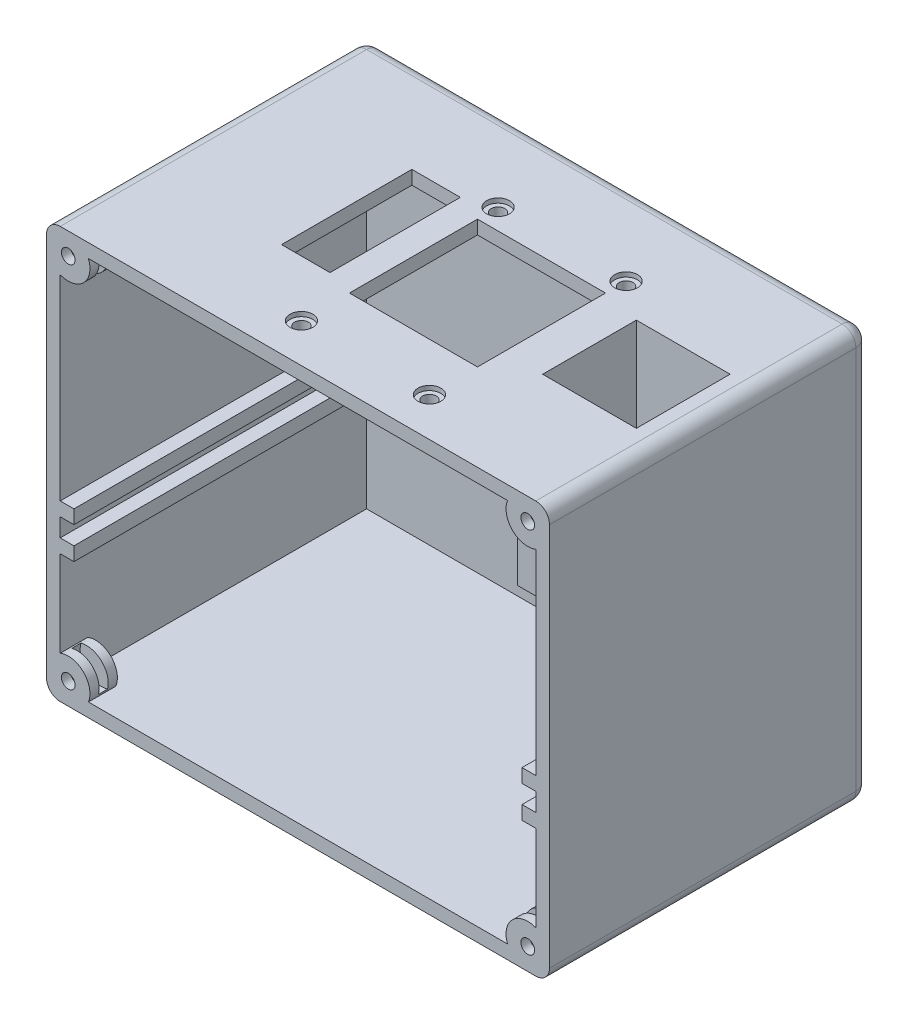
SolidWorks part; units mm, degrees
ref_plane "Płaszczyzna przednia" through (0, 0, 0) normal (0, 0, 1) x (1, 0, 0)
ref_plane "Płaszczyzna górna" through (0, 0, 0) normal (0, 1, 0) x (1, 0, 0)
ref_plane "Płaszczyzna prawa" through (0, 0, 0) normal (1, 0, 0) x (0, 0, -1)
sketch "Sketch2" plane through (0, 0, 0) normal (0, 0, 1) x (1, 0, 0)
  line L1 (55, -45) -> (-55, -45)
  line L2 (55, -45) -> (55, 45)
  line L3 (55, 45) -> (-55, 45)
  line L4 (-55, -45) -> (-55, 45)
  line L5 (55, -45) -> (-55, 45) construction
  line L6 (55, 45) -> (-55, -45) construction
  point P0 (0, 0)
  dimension "D1" = 110
  dimension "D2" = 90
extrude "Boss-Extrude1" add sketch "Sketch2" along normal blind 70
sketch "Sketch4" plane through (0, 0, 70) normal (0, 0, 1) x (1, 0, 0)
  line L0 (55, 45) -> (-55, 45) construction
  line L1 (52, -42) -> (-52, -42)
  line L2 (52, -42) -> (52, 42)
  line L3 (52, 42) -> (-52, 42)
  line L4 (-52, -42) -> (-52, 42)
  line L5 (52, -42) -> (-52, 42) construction
  line L6 (52, 42) -> (-52, -42) construction
  line L7 (-55, 45) -> (-55, -45) construction
  point P0 (0, 0)
  dimension "D1" = 3
  dimension "D2" = 3
extrude "Cut-Extrude1" cut sketch "Sketch4" against normal blind 67
fillet "Fillet6" radius 3 4 edges at (0, -45, 0) (55, 0, 0) (0, 45, 0) (-55, 0, 0)
fillet "Fillet7" radius 3 2 edges at (54.1213, 44.1213, 0.8787) (55, 45, 36.5)
fillet "Fillet8" radius 3 2 edges at (54.1213, -44.1213, 0.8787) (55, -45, 36.5)
fillet "Fillet9" radius 3 2 edges at (-54.1213, -44.1213, 0.8787) (-55, -45, 36.5)
fillet "Fillet10" radius 3 2 edges at (-54.1213, 44.1213, 0.8787) (-55, 45, 36.5)
sketch "Sketch5" plane through (0, 45, 0) normal (0, 1, 0) x (1, 0, 0)
  line L0 (52, -70) -> (52, -3) construction
  line L1 (26, -22) -> (52, -22)
  line L2 (26, -22) -> (26, -48)
  line L3 (26, -48) -> (52, -48)
  line L4 (52, -22) -> (52, -48)
  line L5 (26, -22) -> (52, -48) construction
  line L6 (26, -48) -> (52, -22) construction
  line L7 (-52, 0) -> (52, 0) construction
  point P0 (39, -35)
  dimension "D1" = 26
  dimension "D2" = 22
extrude "Boss-Extrude2" add sketch "Sketch5" against normal blind 40
sketch "Sketch7" plane through (0, 5, 0) normal (0, -1, 0) x (1, 0, 0)
  line L0 (52, 22) -> (26, 22) construction
  line L1 (28.75, 45.25) -> (49.25, 45.25)
  line L2 (28.75, 45.25) -> (28.75, 24.75)
  line L3 (28.75, 24.75) -> (49.25, 24.75)
  line L4 (49.25, 45.25) -> (49.25, 24.75)
  line L5 (28.75, 45.25) -> (49.25, 24.75) construction
  line L6 (28.75, 24.75) -> (49.25, 45.25) construction
  line L7 (52, 48) -> (52, 22) construction
  point P0 (39, 35)
  dimension "D1" = 20.5
  dimension "D2" = 2.75
  dimension "D3" = 2.75
extrude "Cut-Extrude2" cut sketch "Sketch7" against normal blind 40
sketch "Sketch9" plane through (-55, 0, 0) normal (-1, 0, 0) x (0, 0, 1)
  line L0 (3, -42) -> (70, -42) construction
  line L1 (3, -14) -> (70, -14)
  line L2 (3, -14) -> (3, -17)
  line L3 (3, -17) -> (70, -17)
  line L4 (70, -14) -> (70, -17)
  line L5 (70, 42) -> (70, -42) construction
  line L7 (3, -7) -> (70, -7)
  line L8 (3, -7) -> (3, -10)
  line L9 (3, -10) -> (70, -10)
  line L10 (70, -7) -> (70, -10)
  dimension "D1" = 3
  dimension "D2" = 25
  dimension "D3" = 4
extrude "Boss-Extrude3" add sketch "Sketch9" against normal blind 6
sketch "Sketch10" plane through (55, 0, 0) normal (1, 0, 0) x (0, 0, -1)
  line L0 (-70, -42) -> (-3, -42) construction
  line L1 (-70, -14) -> (-3, -14)
  line L2 (-70, -14) -> (-70, -17)
  line L3 (-70, -17) -> (-3, -17)
  line L4 (-3, -14) -> (-3, -17)
  line L5 (-70, -42) -> (-70, 42) construction
  line L7 (-70, -7) -> (-3, -7)
  line L8 (-70, -7) -> (-70, -10)
  line L9 (-70, -10) -> (-3, -10)
  line L10 (-3, -7) -> (-3, -10)
  dimension "D1" = 3
  dimension "D2" = 25
  dimension "D3" = 4
extrude "Boss-Extrude4" add sketch "Sketch10" against normal blind 6
sketch "Sketch12" plane through (0, 45, 0) normal (0, 1, 0) x (1, 0, 0)
  line L0 (28.75, -45.25) -> (28.75, -24.75) construction
  line L1 (-10.25, -16) -> (22.75, -16) construction
  line L2 (-10.25, -16) -> (-10.25, -64) construction
  line L3 (-10.25, -64) -> (22.75, -64) construction
  line L4 (22.75, -16) -> (22.75, -64) construction
  line L5 (-52, 0) -> (52, 0) construction
  line L7 (-7.75, -23) -> (20.25, -23)
  line L8 (-7.75, -23) -> (-7.75, -51)
  line L9 (-7.75, -51) -> (20.25, -51)
  line L10 (20.25, -23) -> (20.25, -51)
  circle A0 centre (-7.75, -18.5) radius 1.5
  circle A1 centre (20.25, -18.5) radius 1.5
  circle A2 centre (-7.75, -61.5) radius 1.5
  circle A3 centre (20.25, -61.5) radius 1.5
  dimension "D5" = 3
  dimension "D8" = 3
  dimension "D11" = 3
  dimension "D14" = 3
  dimension "D1" = 48
  dimension "D2" = 33
  dimension "D3" = 6
  dimension "D4" = 16
  dimension "D6" = 2.5
  dimension "D7" = 2.5
  dimension "D9" = 2.5
  dimension "D10" = 2.5
  dimension "D12" = 2.5
  dimension "D13" = 2.5
  dimension "D15" = 2.5
  dimension "D16" = 2.5
  dimension "D17" = 28
  dimension "D18" = 2.5
  dimension "D19" = 7
extrude "Cut-Extrude4" cut sketch "Sketch12" against normal blind 6
sketch "Sketch13" plane through (0, 45, 0) normal (0, 1, 0) x (1, 0, 0)
  line L0 (-7.75, -23) -> (-7.75, -51) construction
  line L1 (-24.35, -20.75) -> (-13.75, -20.75)
  line L2 (-24.35, -20.75) -> (-24.35, -49.25)
  line L3 (-24.35, -49.25) -> (-13.75, -49.25)
  line L4 (-13.75, -20.75) -> (-13.75, -49.25)
  line L5 (-52, 0) -> (52, 0) construction
  dimension "D1" = 10.6
  dimension "D2" = 28.5
  dimension "D3" = 6
  dimension "D4" = 20.75
extrude "Cut-Extrude5" cut sketch "Sketch13" against normal blind 6
sketch "Sketch14" plane through (0, 0, 70) normal (0, 0, 1) x (1, 0, 0)
  line L0 (52, 45) -> (-52, 45) construction
  line L1 (-55, 42) -> (-55, -42) construction
  line L2 (55, -42) -> (55, 42) construction
  line L3 (-52, -45) -> (52, -45) construction
  circle A0 centre (-50.25, 40.25) radius 4.75
  circle A1 centre (-50.25, 40.25) radius 1.5
  circle A3 centre (50.25, 40.25) radius 4.75
  circle A5 centre (50.25, 40.25) radius 1.5
  circle A6 centre (-50.25, -40.25) radius 4.75
  circle A8 centre (-50.25, -40.25) radius 1.5
  circle A9 centre (50.25, -40.25) radius 4.75
  circle A11 centre (50.25, -40.25) radius 1.5
  dimension "D1" = 9.5
  dimension "D3" = 3
  dimension "D4" = 9.5
  dimension "D6" = 3
  dimension "D7" = 9.5
  dimension "D9" = 3
  dimension "D10" = 9.5
  dimension "D12" = 3
extrude "Boss-Extrude7" add sketch "Sketch14" against normal blind 6
sketch "Sketch16" plane through (0, 0, 70) normal (0, 0, 1) x (1, 0, 0)
  circle A0 centre (-50.25, 40.25) radius 2.75
  circle A1 centre (-46.8912, 36.8912) radius 4.75
  circle A2 centre (50.25, 40.25) radius 2.75
  circle A3 centre (50.25, 40.25) radius 1.5 construction
  circle A4 centre (-50.25, 40.25) radius 1.5 construction
  circle A5 centre (-50.25, -40.25) radius 2.75
  circle A6 centre (-50.25, -40.25) radius 1.5 construction
  circle A7 centre (50.25, -40.25) radius 2.75
  circle A8 centre (50.25, -40.25) radius 1.5 construction
  circle A10 centre (46.8912, -36.8912) radius 4.75
  arc A12 (52, -35.8341) -> (45.8341, -42) centre (50.25, -40.25) ccw construction
  arc A15 (-52, 35.8341) -> (-45.8341, 42) centre (-50.25, 40.25) ccw construction
  circle A16 centre (46.8912, 36.8912) radius 4.75
  arc A17 (45.8341, 42) -> (52, 35.8341) centre (50.25, 40.25) ccw construction
  circle A18 centre (-46.8912, -36.8912) radius 4.75
  arc A19 (-45.8341, -42) -> (-52, -35.8341) centre (-50.25, -40.25) ccw construction
  arc M6 (52, -35.8341) -> (45.8341, -42) centre (50.25, -40.25) ccw
  arc M8 (-45.8341, -42) -> (-52, -35.8341) centre (-50.25, -40.25) ccw
  arc M18 (-52, 35.8341) -> (-45.8341, 42) centre (-50.25, 40.25) ccw
  arc M20 (45.8341, 42) -> (52, 35.8341) centre (50.25, 40.25) ccw
  circle M37 centre (50.25, -40.25) radius 1.5
  circle M38 centre (-50.25, 40.25) radius 1.5
  circle M39 centre (50.25, 40.25) radius 1.5
  circle M40 centre (-50.25, -40.25) radius 1.5
  dimension "D1" = 5.5
  dimension "D2" = 5.5
  dimension "D3" = 5.5
  dimension "D4" = 5.5
extrude "Cut-Extrude6" cut sketch "Sketch16" against normal blind 2 from offset 2 contours A18 A5 M40 | A18 M8 | A18 A5 M8 | A5 A18 M40 | A10 A7 M37 | A7 A10 M37 | A10 A7 M6 | A10 M6 | A16 A2 M39 | A2 A16 M39 | A2 A16 M20 | A16 M20 | A1 M18 | A1 A0 M18 | A0 A1 M38 | A1 A0 M38 region at (-49.1285, 39.1285, 70) region at (-48.1128, 38.1128, 70) region at (-48.4686, 41.4492, 70) region at (-45.813, 35.813, 70) region at (52.5466, 38.8748, 70) region at (49.1285, 39.1285, 70) region at (48.1128, 38.1128, 70) region at (45.813, 35.813, 70) region at (-49.1285, -39.1285, 70) region at (-48.1128, -38.1128, 70) region at (-51.4492, -38.4686, 70) region at (-45.813, -35.813, 70) region at (50.9015, -42.8463, 70) region at (49.1285, -39.1285, 70) region at (48.1128, -38.1128, 70) region at (45.813, -35.813, 70) offset against normal yes
sketch "Sketch17" plane through (0, 45, 0) normal (0, 1, 0) x (1, 0, 0)
  circle A0 centre (-7.75, -18.5) radius 2.5
  circle A1 centre (-7.75, -18.5) radius 1.5 construction
  circle A2 centre (20.25, -18.5) radius 2.5
  circle A3 centre (20.25, -18.5) radius 1.5 construction
  circle A4 centre (-7.75, -61.5) radius 2.5
  circle A5 centre (-7.75, -61.5) radius 1.5 construction
  circle A6 centre (20.25, -61.5) radius 2.5
  circle A7 centre (20.25, -61.5) radius 1.5 construction
  dimension "D1" = 5
  dimension "D2" = 5
  dimension "D3" = 5
  dimension "D4" = 5
extrude "Cut-Extrude11" cut sketch "Sketch17" against normal blind 1
